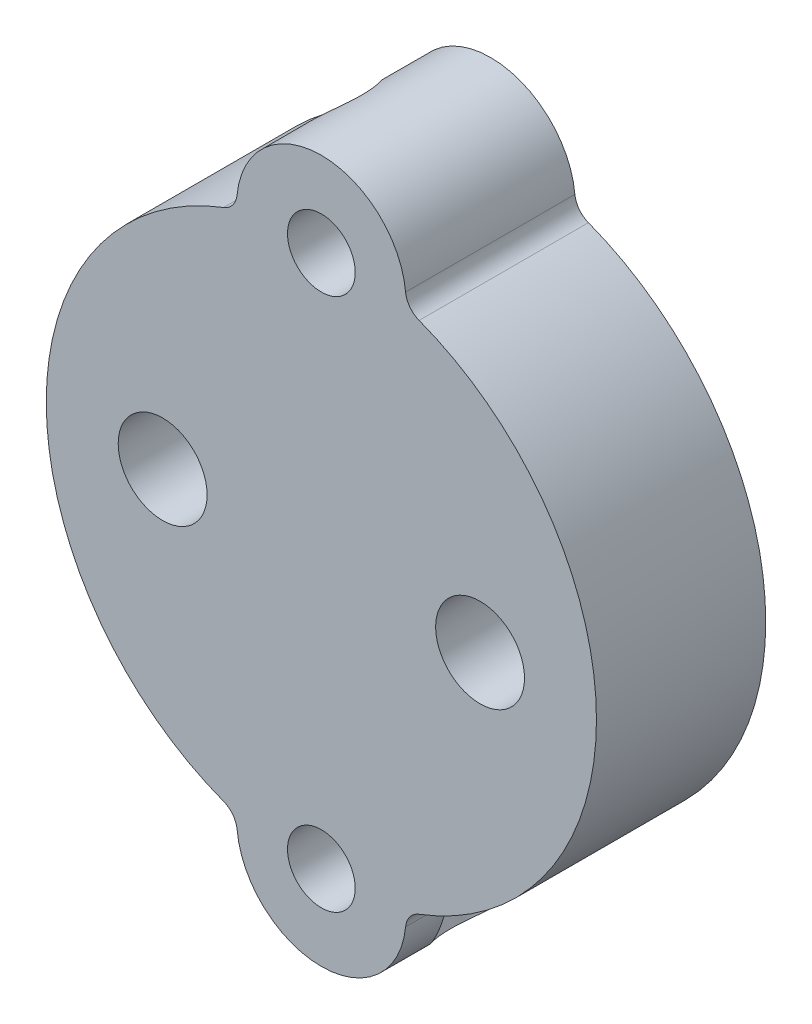
SolidWorks part; units mm, degrees
ref_plane "Front Plane" through (0, 0, 0) normal (0, 0, 1) x (1, 0, 0)
ref_plane "Top Plane" through (0, 0, 0) normal (0, 1, 0) x (1, 0, 0)
ref_plane "Right Plane" through (0, 0, 0) normal (1, 0, 0) x (0, 0, -1)
sketch "Sketch1" plane through (0, 0, 0) normal (0, 0, 1) x (1, 0, 0)
  line L0 (0, 12.6) -> (0, -12.6) construction
  line L1 (-7.5, 0) -> (7.5, 0) construction
  arc A2 (4.6209, -12.151) -> (4.6209, 12.151) centre (0, 0) ccw
  circle A4 centre (0, 12.6) radius 1.6
  circle A5 centre (0, -12.6) radius 1.6
  circle A6 centre (7.5, 0) radius 2.1
  circle A7 centre (-7.5, 0) radius 2.1
  arc A42 (-3.9811, -12.9886) -> (3.9811, -12.9886) centre (0, -12.6) ccw
  arc A44 (-4.6209, 12.151) -> (-4.6209, -12.151) centre (0, 0) ccw
  arc A46 (3.9811, 12.9886) -> (-3.9811, 12.9886) centre (0, 12.6) ccw
  arc A150 (-3.9811, -12.9886) -> (-4.6209, -12.151) centre (-4.9764, -13.0857) ccw
  arc A152 (-4.6209, 12.151) -> (-3.9811, 12.9886) centre (-4.9764, 13.0857) ccw
  arc A154 (3.9811, 12.9886) -> (4.6209, 12.151) centre (4.9764, 13.0857) ccw
  arc A156 (4.6209, -12.151) -> (3.9811, -12.9886) centre (4.9764, -13.0857) ccw
  point P11 (0, 0)
  dimension "D3" = 4.2
  dimension "D4" = 3.2
  dimension "D5" = 4
  dimension "D1" = 13
  dimension "D6" = 1
  dimension "D2" = 15
  dimension "D7" = 3.9811
extrude "Boss-Extrude1" add sketch "Sketch1" along normal blind 8
ref_axis "Axis1" through (0, 0, -0.4) along (0, 0, 1)
ref_plane "Plane2" through (0, 0, 0) normal (-0.2588, 0.9659, 0) x (0, 0, 1)
sketch "Sketch3" plane through (0, 0, 0) normal (-0.2588, 0.9659, 0) x (0, 0, 1)
  line L0 (8, 13) -> (0, 13) construction
  circle A0 centre (4, 0) radius 2.1
  point P4 (4, 13)
  dimension "D1" = 4.2
extrude "Cut-Extrude1" cut sketch "Sketch3" against normal through all both and the other way through all
sketch "Sketch4" plane through (0, 0, 0) normal (0, 0, -1) x (-1, 0, 0)
  circle A0 centre (-7.5, 0) radius 3.4
  circle A1 centre (7.5, 0) radius 3.4
  circle A2 centre (7.5, 0) radius 2.1 construction
  dimension "D1" = 6.8
extrude "Cut-Extrude2" cut sketch "Sketch4" against normal blind 3 and the other way through all
